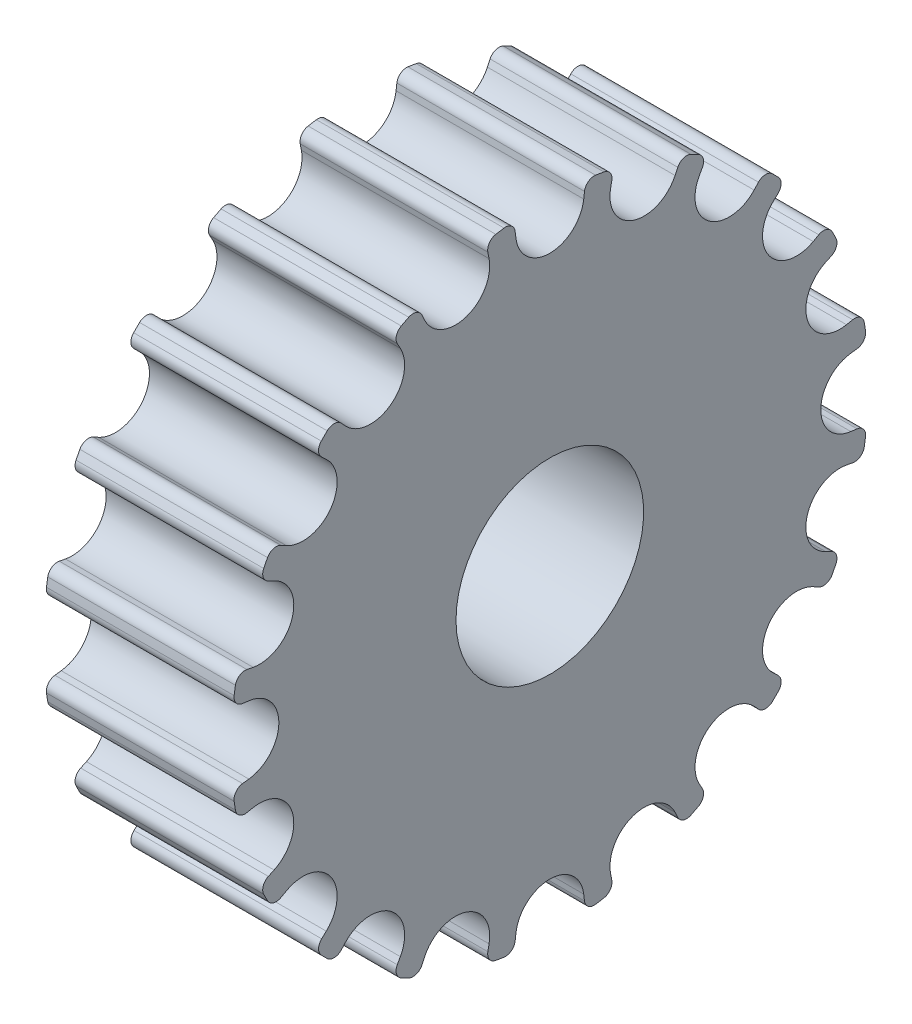
SolidWorks part; units mm, degrees
ref_plane "前视基准面" through (0, 0, 0) normal (0, 0, 1) x (1, 0, 0)
ref_plane "上视基准面" through (0, 0, 0) normal (0, 1, 0) x (1, 0, 0)
ref_plane "右视基准面" through (0, 0, 0) normal (1, 0, 0) x (0, 0, -1)
sketch "草图1" plane through (0, 0, 0) normal (0, 0, 1) x (1, 0, 0)
  line L0 (0, 0) -> (64.8368, 0) construction
  line L1 (0, 1.8338) -> (0, 8.5)
  line L2 (0, 8.5) -> (5, 8.5)
  line L3 (5, 8.5) -> (5, 3.6676)
  line L4 (5, 3.6676) -> (20, 3.6676)
  line L5 (20, 3.6676) -> (20, 1.8338)
  line L6 (20, 1.8338) -> (0, 1.8338)
  dimension "L" = 20
  dimension "B" = 5
  dimension "d" = 3.6676
  dimension "d1" = 7.3352
  dimension "da" = 17
revolve "旋转1" add sketch "草图1" angle 360 about L0
chamfer "倒角1" distance 1 angle 45 2 edges at (20, 0, 1.8338) (0, 0, 1.8338)
sketch "草图4" plane through (0, 0, 0) normal (-1, 0, 0) x (0, 0, 1)
  line L1 (-1, 1.5371) -> (1, 1.5371)
  line L2 (-1, 1.5371) -> (-1, 2.5371)
  line L3 (-1, 2.5371) -> (1, 2.5371)
  line L4 (1, 1.5371) -> (1, 2.5371)
  circle A0 centre (0, 0) radius 1.8338 construction
  dimension "键槽宽度" = 2
  dimension "t1" = 1
extrude "切除-拉伸1" cut sketch "草图4" against normal through all
ref_axis "基准轴1" through (-1.4, 0, 0) along (1, 0, 0)
sketch "草图6" plane through (0, 0, 0) normal (1, 0, 0) x (0, 0, -1)
  line L0 (0, 0) -> (0, 30.6512) construction
  line L1 (0.9238, 8.1865) -> (0.9032, 8.0191)
  line L2 (1.4758, 8.3709) -> (1.6725, 9.9725)
  line L3 (-1.4758, 8.3709) -> (-1.6725, 9.9725)
  line L4 (-0.9238, 8.1865) -> (-0.9032, 8.0191)
  circle A0 centre (0, 0) radius 8.5 construction
  circle A1 centre (0, 0) radius 7.22 construction
  arc A2 (-0.9032, 8.0191) -> (0.9032, 8.0191) centre (0, 8.13) ccw
  arc A3 (1.6725, 9.9725) -> (-1.6725, 9.9725) centre (0, 0) ccw
  arc A4 (0.9238, 8.1865) -> (1.2191, 8.4121) centre (1.1818, 8.1548) cw
  arc A5 (1.2191, 8.4121) -> (1.4758, 8.3709) centre (0, 0) cw
  arc A6 (-1.2191, 8.4121) -> (-1.4758, 8.3709) centre (0, 0) ccw
  arc A7 (-0.9238, 8.1865) -> (-1.2191, 8.4121) centre (-1.1818, 8.1548) ccw
  point P7 (0, 1.9)
  point P8 (0, 29.3712)
  point P15 (0.9556, 8.4461)
  dimension "D1" = 14.44
  dimension "ra" = 0.26
  dimension "rf" = 0.91
  dimension "hg" = 1.28
  dimension "D3" = 0.26
  dimension "D4" = 1.6136
  dimension "angle" = 14
  dimension "bw" = 1.9
extrude "切除-拉伸2" cut sketch "草图6" along normal up to next
pattern_circular "阵列(圆周)3" count 20 over 360 about axis through (-1.4, 0, 0) along (1, 0, 0) of "切除-拉伸2"
sketch "草图7" plane through (0, 0, 0) normal (-1, 0, 0) x (0, 0, 1)
  circle A0 centre (0, 0) radius 2.8338
extrude "切除-拉伸3" cut sketch "草图7" against normal through all
sketch "草图8" plane through (20, 0, 0) normal (1, 0, 0) x (0, 0, -1)
  circle A0 centre (0, 0) radius 3.6676
extrude "切除-拉伸4" cut sketch "草图8" against normal up to surface (15 mm away) up to face at (5, 0, 3.6676)
sketch "草图9" plane through (0, 0, 0) normal (-1, 0, 0) x (0, 0, 1)
  circle A0 centre (0, 0) radius 2.5
  circle A1 centre (0, 0) radius 2.8338
  dimension "D1" = 5
extrude "凸台-拉伸1" add sketch "草图9" against normal up to surface (5 mm away) up to face at (5, 0, 0)
equation "\"D1@草图6\" = \"da@草图1\"  - \"hg@草图6\" - \"hg@草图6\""
equation "\"D3@草图6\" = \"ra@草图6\""
